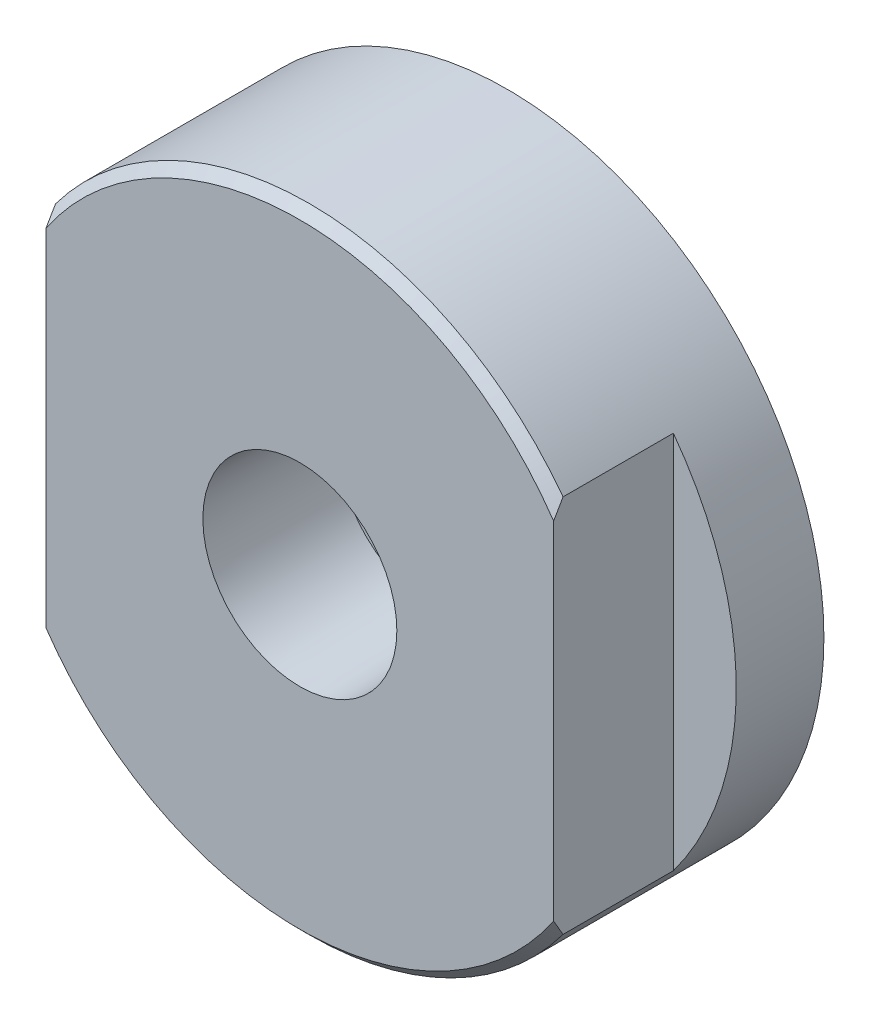
SolidWorks part; units mm, degrees
note: '?' marks a value the reader was unsure of.
ref_plane "Front" through (0, 0, 0) normal (0, 0, 1) x (1, 0, 0)
ref_plane "Top" through (0, 0, 0) normal (0, 1, 0) x (1, 0, 0)
ref_plane "Right" through (0, 0, 0) normal (1, 0, 0) x (0, 0, -1)
sketch "Sketch1" plane through (0, 0, 0) normal (0, 0, 1) x (1, 0, 0)
  circle A0 centre (0, 0) radius 16.8
  dimension "D1" = 33.6
extrude "Body" add sketch "Sketch1" along normal blind 11
chamfer "BodyChamfer" distance 0.5 angle 45 1 edges at (16.8, 0, 11)
sketch "Sketch2" plane through (0, 0, 11) normal (0, 0, 1) x (1, 0, 0)
  line L0 (-13.462, -10.0506) -> (-13.462, 10.0506)
  line L1 (0, -16.3) -> (0, 16.3) construction
  line L2 (13.462, -10.0506) -> (13.462, 10.0506)
  circle A0 centre (0, 0) radius 16.3 construction
  circle A1 centre (0, 0) radius 16.8 construction
  arc A2 (-13.462, 10.0506) -> (-13.462, -10.0506) centre (0, 0) ccw
  arc A3 (13.462, 10.0506) -> (13.462, -10.0506) centre (0, 0) cw
  dimension "D1" = 13.462
extrude "BodyFlat" cut sketch "Sketch2" against normal blind 6.35
hole_wizard "1/8 NPT Tapped Hole1" positions "3DSketch1" profile "Sketch4" size "1/8" standard "Ansi Inch"
sketch3d "3DSketch1"
  arc A0 (-13.462, 10.0506, 10.5) -> (13.462, 10.0506, 10.5) centre (0, 0, 10.5) ccw construction
  point P0 (0, 0, 11)
  point P6 (0, 0, -6.3)
sketch "Sketch4" plane through (0, 0, 11) normal (1, 0, 0) x (0, -1, 0)
  line L0 (0, 0) -> (0, 14.5335)
  line L1 (4.2164, 12) -> (0, 14.5335)
  line L2 (-4.2164, 12) -> (0, 14.5335) construction
  line L3 (4.2164, 12) -> (4.2164, 7)
  line L4 (4.2164, 7) -> (4.9362, 7)
  line L5 (4.9362, 7) -> (5.1458, 0)
  line L6 (-4.9362, 7) -> (-5.1458, 0) construction
  line L7 (5.1458, 0) -> (0, 0)
  line L8 (0, -6.35) -> (0, 107.95) construction
  line L11 (-4.2164, 7) -> (-4.9362, 7) construction
  dimension "Tap Drill Dia." = 8.4328
  dimension "Tap Drill Depth" = 12
  dimension "Thread Dia." = 10.2915
  dimension "Thread Angle" = 3.43
  dimension "Thread Depth" = 7
  dimension "Drill Angle" = 118
sketch "Sketch5" plane through (0, 0, 11) normal (0, 0, 1) x (1, 0, 0)
  circle A0 centre (0, 0) radius 7.9
  dimension "D1" = 15.8
extrude "MaleThread" [suppressed] add sketch "Sketch5" along normal blind 16
sketch "Sketch6" [suppressed] plane through (0, 0, 21) normal (0, 0, 1) x (1, 0, 0)
  line L0 (6.3125, -4.75) -> (-6.3125, -4.75)
  line L1 (-7.9, 0) -> (7.9, 0) construction
  line L2 (6.3125, 4.75) -> (-6.3125, 4.75)
  arc A2 (-6.3125, -4.75) -> (6.3125, -4.75) centre (0, 0) ccw
  arc A3 (-6.3125, 4.75) -> (6.3125, 4.75) centre (0, 0) cw
  circle A4 centre (0, 0) radius 7.9 construction
  circle A5 centre (0, 0) radius 7.9 construction
  dimension "D1" = 9.5
extrude "ThreadFlat" [suppressed] cut sketch "Sketch6" against normal blind 15.7
chamfer "ThreadChamfer" [suppressed] distance 1.2 angle 45
sketch "Sketch7" [suppressed] plane through (0, 0, 0) normal (0, 1, 0) x (0, 0, -1)
  line L0 (-10, 7.9) -> (-10, 7.8)
  line L1 (-5, 7.9) -> (-19.8, 7.9) construction
  line L2 (-9.2, 7) -> (-8, 7)
  line L3 (-7.2, 7.8) -> (-7.2, 7.9)
  line L4 (-7.2, 7.9) -> (-10, 7.9)
  line L6 (-21, 0) -> (0, 0) construction
  line L7 (-21, 4.7252) -> (-21, -4.7252) construction
  arc A0 (-10, 7.8) -> (-9.2, 7) centre (-9.2, 7.8) ccw
  arc A1 (-7.2, 7.8) -> (-8, 7) centre (-8, 7.8) cw
  point P14 (-10, 7)
  point P17 (-7.2, 7)
  dimension "D4" = 0.8
  dimension "D1" = 14
  dimension "D2" = 2.8
  dimension "D3" = 13.8
revolve "ThreadEnd" [suppressed] cut sketch "Sketch7" angle 360 about L6
sketch "Sketch8" [suppressed] plane through (0, 4.75, 0) normal (0, 1, 0) x (0, 0, -1)
  line L0 (0, -10.3) -> (0, 10.3) construction
  circle A0 centre (-13.888, 0) radius 3.2
  dimension "D1" = 6.4
  dimension "D2" = 8.6
extrude "PivotpinHole" [suppressed] cut sketch "Sketch8" against normal up to next
chamfer "Chamfer3" [suppressed] distance 0.5 angle 45
ref_plane "PortPlane" [suppressed] through (0, 10.9, 0) normal (0, 1, 0) x (0, 0, -1)
hole_wizard "1/8 NPT Tapped Hole2" [suppressed] positions "Sketch10" profile "Sketch9" size "1/8" standard "Ansi Inch"
sketch "Sketch10" plane through (0, 10.9, 0) normal (0, 1, 0) x (0, 0, -1)
  line L0 (0, -10.9) -> (0, 10.9) construction
  point P1 (-11, 0)
  dimension "D1" = 9.5
sketch "Sketch9" [suppressed] plane through (0, 10.9, 11) normal (1, 0, 0) x (0, 0, 1)
  line L0 (0, 0) -> (0, 17.2325)
  line L1 (4.2164, 14.699) -> (0, 17.2325)
  line L2 (-4.2164, 14.699) -> (0, 17.2325) construction
  line L3 (4.2164, 14.699) -> (4.2164, 10)
  line L4 (4.2164, 10) -> (4.9362, 10)
  line L5 (4.9362, 10) -> (5.2356, 0)
  line L6 (-4.9362, 10) -> (-5.2356, 0) construction
  line L7 (5.2356, 0) -> (0, 0)
  line L8 (0, -6.35) -> (0, 107.95) construction
  line L11 (-4.2164, 10) -> (-4.9362, 10) construction
  dimension "Tap Drill Dia." = 8.4328
  dimension "Tap Drill Depth" = 14.699
  dimension "Thread Dia." = 10.4712
  dimension "Thread Angle" = 3.43
  dimension "Thread Depth" = 10
  dimension "Drill Angle" = 118
ref_axis "Axis1" [suppressed] through (0, 10.9, 11) along (0, -1, 0)?
sketch "Sketch11" [suppressed] plane through (0, 0, 0) normal (1, 0, 0) x (0, 0, -1)
  line L0 (-17.6, 10.9) -> (-16.2, 10.9)
  line L1 (-16.2356, 10.9) -> (-17.8, 10.9) construction
  line L2 (-16.2, 10.9) -> (-16.2, 9.5)
  line L3 (-16.2, 9.5) -> (-17.6, 10.9)
  line L4 (-18, 10.7) -> (-18, -10.7) construction
  dimension "D1" = 45
  dimension "D2" = 1.25
  dimension "D3" = 1.9
revolve "PortChamfer" [suppressed] cut sketch "Sketch11" angle 360 about axis through (0, 10.9, 11) along (0, -1, 0)
